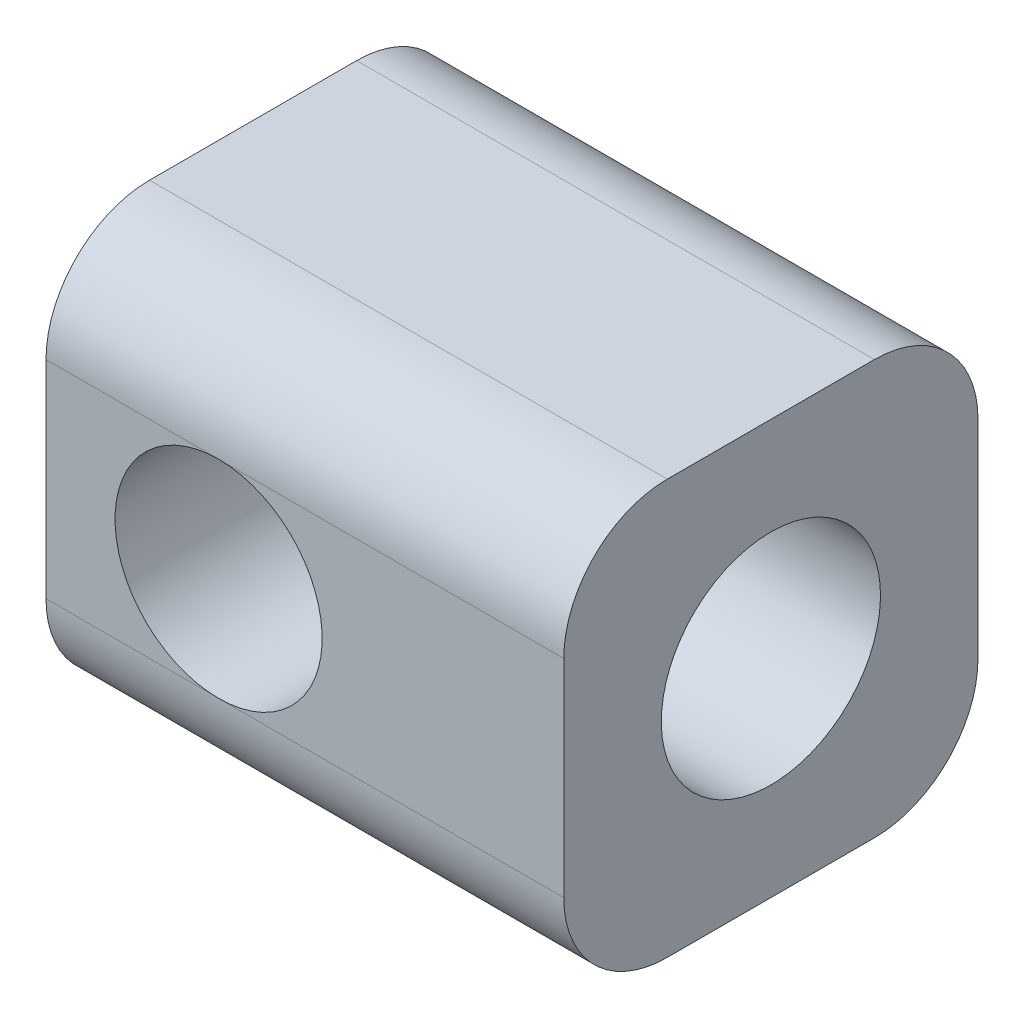
SolidWorks part; units mm, degrees
ref_plane "Front Plane" through (0, 0, 0) normal (0, 0, 1) x (1, 0, 0)
ref_plane "Top Plane" through (0, 0, 0) normal (0, 1, 0) x (1, 0, 0)
ref_plane "Right Plane" through (0, 0, 0) normal (1, 0, 0) x (0, 0, -1)
sketch "Sketch1" plane through (0, 0, 0) normal (0, 0, 1) x (1, 0, 0)
  line L0 (0, 0) -> (-5, 0) construction
  line L1 (10, 6) -> (-5, 6)
  line L2 (10, 6) -> (10, -6)
  line L3 (10, -6) -> (-5, -6)
  line L4 (-5, 6) -> (-5, -6)
  circle A0 centre (0, 0) radius 3
  dimension "D1" = 6
  dimension "D2" = 12
  dimension "D3" = 5
  dimension "D4" = 10
extrude "Boss-Extrude1" add sketch "Sketch1" along normal blind 12
sketch "Sketch2" plane through (10, 0, 0) normal (1, 0, 0) x (0, 0, -1)
  line L0 (-6, 0) -> (-6, 6) construction
  line L1 (-12, 6) -> (0, 6) construction
  line L2 (-6, 0) -> (0, 0) construction
  line L3 (0, -6) -> (0, 6) construction
  circle A0 centre (-6, 0) radius 3.175
  dimension "D1" = 6.35
extrude "Cut-Extrude1" cut sketch "Sketch2" against normal blind 10
sketch "Sketch3" plane through (0, 0, 0) normal (0, 1, 0) x (1, 0, 0)
  line L0 (0, 0) -> (0, -6) construction
  line L1 (0, -6) -> (10, -6) construction
fillet "Fillet1" radius 3 4 edges at (2.5, -6, 0) (2.5, -6, 12) (2.5, 6, 12) (2.5, 6, 0)
